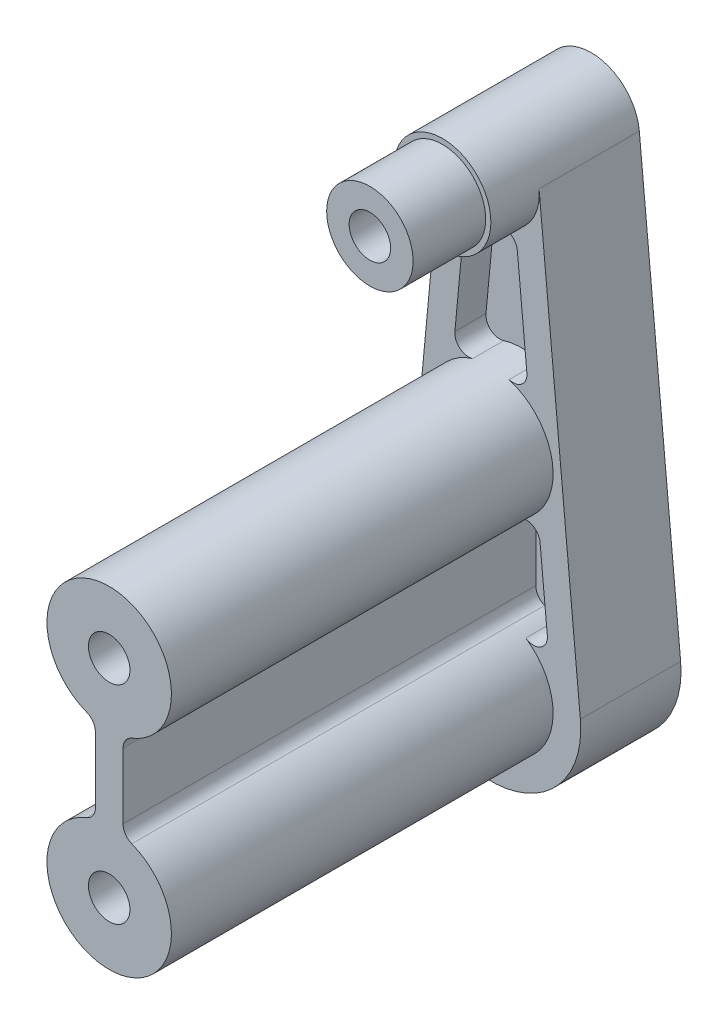
SolidWorks part; units mm, degrees
material "ABS"
ref_plane "Front Plane" through (0, 0, 0) normal (0, 0, 1) x (1, 0, 0)
ref_plane "Top Plane" through (0, 0, 0) normal (0, 1, 0) x (1, 0, 0)
ref_plane "Right Plane" through (0, 0, 0) normal (1, 0, 0) x (0, 0, -1)
sketch "Sketch1" plane through (0, 0, 0) normal (0, 0, 1) x (1, 0, 0)
  line L0 (0, 32) -> (0, 0) construction
  line L1 (-3.4846, 32.3281) -> (-6.4714, 0.6094)
  line L2 (6.4714, 0.6094) -> (3.4846, 32.3281)
  circle A0 centre (0, 0) radius 1.5
  circle A1 centre (0, 15) radius 1.5
  circle A2 centre (0, 32) radius 1.5
  circle A3 centre (0, 0) radius 4.5
  circle A4 centre (0, 15) radius 4.5
  circle A5 centre (0, 0) radius 6.5
  circle A6 centre (0, 32) radius 3.125
  circle A7 centre (0, 32) radius 3.5
  dimension "D1" = 3
  dimension "D4" = 3
  dimension "D5" = 3
  dimension "D6" = 7
  dimension "Bearing_ID" = 6.25
  dimension "D7" = 2
  dimension "D2" = 17
  dimension "D3" = 15
extrude "Boss-Extrude1" add sketch "Sketch1" along normal blind 5 contours L0 A7 L1 A5 A4 | A7 L0 A4 A5 L2 | A7 | A4 | A1 | A2 | A5 | A0 region at (2.7038, 29.2962, 0) region at (-0.3237, 24, 0)
extrude "Boss-Extrude3" add sketch "Sketch1<5>" along normal blind 5.75 from surface contours A6 A7 | A2 A6 region at (0, 35.401, 0) region at (-3.0366, 32, 0) starting at face at (0, 15.4844, 5)
sketch "Sketch1<5>" plane through (0, 0, 0) normal (0, 0, 1) x (1, 0, 0) same geometry as "Sketch1"
extrude "Boss-Extrude2" add sketch "Sketch1<4>" along normal blind 5.25 from surface contours A2 A6 region at (-3.0366, 32, 0) starting at face at (3.5, 32, 10.75)
sketch "Sketch1<4>" plane through (0, 0, 0) normal (0, 0, 1) x (1, 0, 0) same geometry as "Sketch1"
extrude "Boss-Extrude4" add sketch "Sketch1<6>" along normal blind 29.85 from surface contours A4 L0 A1 | A3 A0 | L0 A4 A1 region at (2.069, 15, 0) region at (-2.069, 15, 0) region at (3.092, 3.092, 0) starting at face at (0, 13.7344, 5)
sketch "Sketch1<6>" plane through (0, 0, 0) normal (0, 0, 1) x (1, 0, 0) same geometry as "Sketch1"
sketch "Sketch2" plane through (0, 0, 5) normal (0, 0, 1) x (1, 0, 0)
  line L19 (-1.4934, 32.1406) -> (-4.4802, 0.4219)
  line L20 (-1.7899, 28.9923) -> (-4.4802, 0.4219)
  line L22 (4.4802, 0.4219) -> (1.4934, 32.1406)
  line L23 (4.4802, 0.4219) -> (1.7899, 28.9923)
  line L24 (-1, 28.6459) -> (1, 28.6459)
  line L25 (-1, 28.6459) -> (-1, 4.3875)
  line L26 (-1, 4.3875) -> (1, 4.3875)
  line L27 (1, 28.6459) -> (1, 4.3875)
  circle A13 centre (0, 32) radius 3.5
  circle A14 centre (0, 32) radius 3.5 construction
  circle A15 centre (0, 0) radius 4.5
  circle A16 centre (0, 0) radius 4.5 construction
  circle A17 centre (0, 15) radius 4.5
  circle A18 centre (0, 15) radius 4.5 construction
  circle M5 centre (0, 0) radius 4.5
  line M6 (6.4714, 0.6094) -> (3.4846, 32.3281)
  arc M7 (3.4846, 32.3281) -> (-3.4846, 32.3281) centre (0, 32) cw
  line M8 (-3.4846, 32.3281) -> (-6.4714, 0.6094)
  arc M9 (-6.4714, 0.6094) -> (6.4714, 0.6094) centre (0, 0) ccw
  circle M10 centre (0, 15) radius 4.5
  dimension "D3" = 2
  dimension "D1" = 2
  dimension "D2" = 2
extrude "Boss-Extrude5" add sketch "Sketch2" along normal blind 2.25 contours A15 L20 L23 M7 M8 M9 M6 | L23 M10 region at (-2.6895, 23.8063, 5) region at (3.6484, 15.3436, 5)
extrude "Boss-Extrude6" add sketch "Sketch2<3>" along normal up to surface (29.85 mm away) contours L27 L25 M10 M5 region at (0, 7.5, 5) up to face at (4.5, 15, 34.85)
sketch "Sketch2<3>" plane through (0, 0, 5) normal (0, 0, 1) x (1, 0, 0) same geometry as "Sketch2"
fillet "Fillet1" radius 1 12 edges at (-1.7899, 28.9923, 6.125) (1.7899, 28.9923, 6.125) (4.4802, 0.4219, 6.125) (-4.4802, 0.4219, 6.125) (3.3865, 12.0366, 6.125) (-3.3865, 12.0366, 6.125) (2.7738, 18.5435, 6.125) (-2.7738, 18.5435, 6.125) (1, 4.3875, 19.925) (1, 10.6125, 19.925) (-1, 4.3875, 19.925) (-1, 10.6125, 19.925)
equation "\"D2@Sketch2\"=\"D1@Sketch2\""
